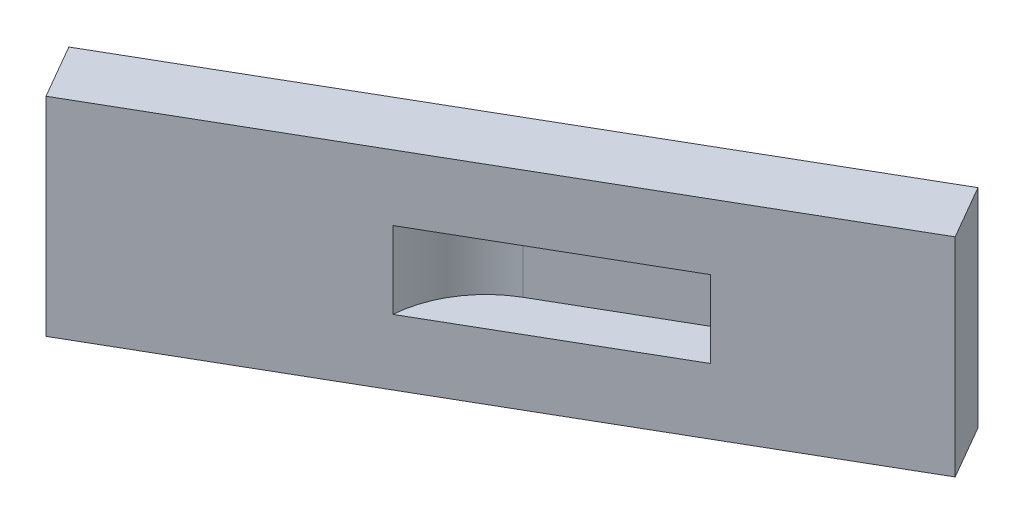
SolidWorks part; units mm, degrees
ref_plane "前基準面" through (0, 0, 0) normal (0, 0, 1) x (1, 0, 0)
ref_plane "上基準面" through (0, 0, 0) normal (0, 1, 0) x (1, 0, 0)
ref_plane "右基準面" through (0, 0, 0) normal (1, 0, 0) x (0, 0, -1)
sketch "草圖2" plane through (0, 0, 0) normal (0, 1, 0) x (1, 0, 0)
  line L0 (3.2953, 10.0619) -> (-24.4175, -5.9381)
  line L1 (-12.0611, 4.66) -> (-8.3978, -1.6851) construction
  line L2 (1.7953, 12.66) -> (-25.9175, -3.34)
  line L3 (-8.3978, -1.6851) -> (-8.3978, 11.5289) construction
  line L4 (-25.9175, -3.34) -> (-24.4175, -5.9381)
  line L5 (1.7953, 12.66) -> (3.2953, 10.0619)
  line L6 (-15.3563, -0.7066) -> (-15.3563, 2.4) construction
  line L7 (-25.9175, -3.34) -> (-27.4175, -0.7419)
  line L8 (-27.4175, -0.7419) -> (0.2953, 15.2581)
  line L9 (0.2953, 15.2581) -> (1.7953, 12.66)
  line L10 (-15.3563, -29.6) -> (-15.3563, 2.4) construction
  line L11 (-12.9313, 6.6002) -> (-5.6563, 10.8004) construction
  line L12 (-5.6563, 4.8937) -> (-5.6563, 10.8004) construction
  line L13 (-15.3563, -0.7066) -> (-15.3563, 2.4)
  line L14 (-12.9313, 6.6002) -> (-5.6563, 10.8004)
  line L15 (-5.6563, 10.8004) -> (-5.6563, 4.8937)
  line L16 (-15.3563, -0.7066) -> (-5.6563, 4.8937)
  arc A0 (-15.3563, 2.4) -> (-12.9313, 6.6002) centre (-10.5063, 2.4) cw construction
  arc A1 (-15.3563, 2.4) -> (-12.9313, 6.6002) centre (-10.5063, 2.4) cw
  dimension "D1" = 30
  dimension "D2" = 9.7
  dimension "D4" = 32
  dimension "D5" = 32
extrude "填料-伸長1" add sketch "草圖2" along normal blind 5 and the other way blind 5 contours L2 A0 L9 L8 L7 | A0 L2 region at (-2.1037, 0, -10.8088) region at (-10.262, 0, -6.8842)
extrude "除料-伸長1" cut sketch "草圖2<7>" against normal mid plane 3.7 contours L13 A1 L14 L15 L16
sketch "草圖2<7>" plane through (0, 0, 0) normal (0, 1, 0) x (1, 0, 0) same geometry as "草圖2"
